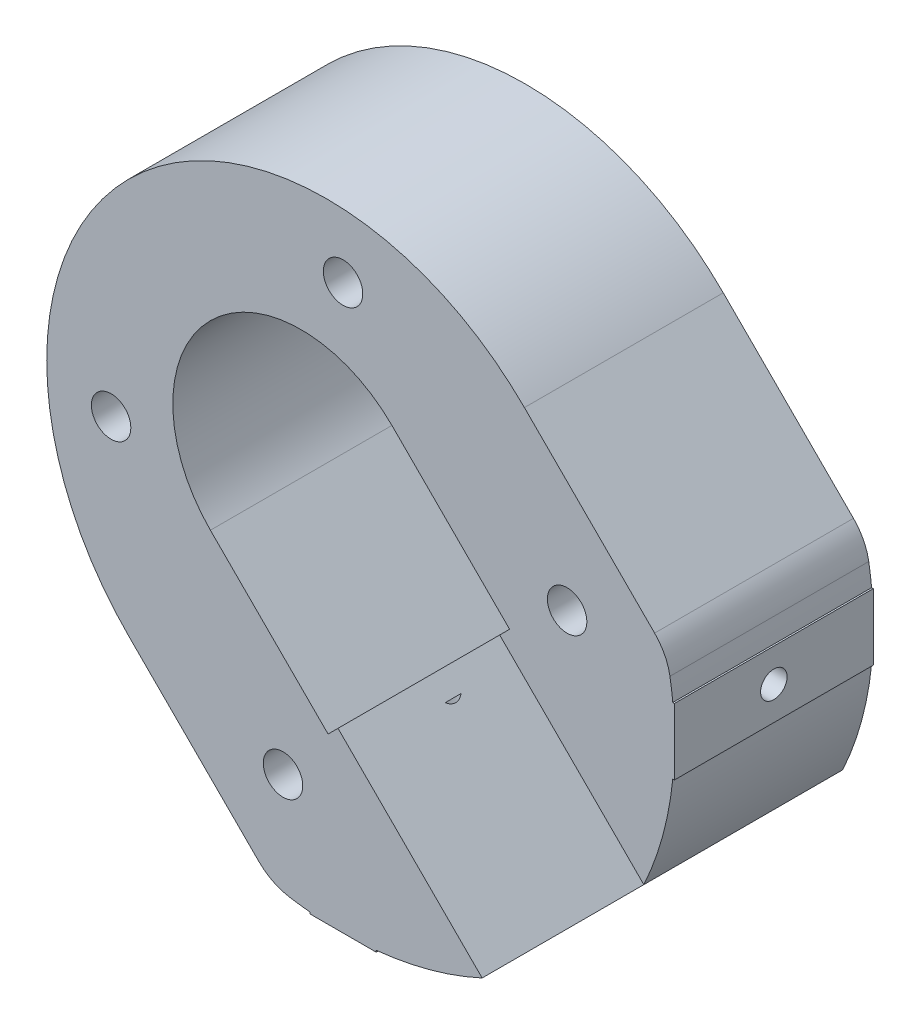
SolidWorks part; units mm, degrees
ref_plane "Front Plane" through (0, 0, 0) normal (0, 0, 1) x (1, 0, 0)
ref_plane "Top Plane" through (0, 0, 0) normal (0, 1, 0) x (1, 0, 0)
ref_plane "Right Plane" through (0, 0, 0) normal (1, 0, 0) x (0, 0, -1)
ref_axis "Z" through (0, 0, 33.5996) along (0, 0, -1)
ref_axis "X" through (56.0652, 0, 0) along (-1, 0, 0)
ref_axis "Y" through (0, -54.2845, 0) along (0, 1, 0)
sketch "Sketch1" plane through (0, 0, 0) normal (0, 0, 1) x (1, 0, 0)
  line L0 (5, -50) -> (-5, -50)
  line L1 (50, 5) -> (50, -5)
  line L2 (56.0652, 0) -> (-1.1166, 0) construction
  line L3 (0, -54.2845) -> (0, 1.1167) construction
  line L4 (61.712, 0) -> (50, 0) construction
  line L5 (0, -50) -> (0, -57.4075) construction
  line L6 (50, -5) -> (49.7494, -5)
  line L7 (5, -49.7494) -> (5, -50)
  line L10 (65.572, -65.572) -> (0, 0) construction
  line L20 (-5, -50) -> (-5, -49.7494)
  line L21 (49.7494, 5) -> (50, 5)
  line L22 (20.987, -45.3822) -> (-0.7634, -23.6318)
  line L23 (45.3822, -20.987) -> (23.6318, 0.7634)
  line L25 (-0.7634, -23.6318) -> (-2.2604, -25.1287)
  line L26 (-2.2604, -25.1287) -> (-20.0175, -7.3715)
  line L27 (23.6318, 0.7634) -> (25.1287, 2.2604)
  line L28 (25.1287, 2.2604) -> (7.3715, 20.0175)
  line L29 (-12.6985, -47.012) -> (-32.3444, -27.3661)
  line L30 (47.012, 12.6985) -> (27.3661, 32.3444)
  circle A0 centre (0, 0) radius 50 construction
  circle A1 centre (0, 0) radius 3.535 construction
  arc A2 (49.7494, -5) -> (5, -49.7494) centre (0, 0) cw construction
  arc A6 (49.7494, 5) -> (49.3214, 8.2098) centre (0, 0) ccw
  arc A7 (5, -49.7494) -> (20.987, -45.3822) centre (0, 0) ccw
  arc A8 (49.7494, -5) -> (45.3822, -20.987) centre (0, 0) cw
  arc A9 (7.3715, 20.0175) -> (-20.0175, -7.3715) centre (-6.323, 6.323) ccw
  arc A10 (-8.2098, -49.3214) -> (-12.6985, -47.012) centre (-6.8523, -41.1658) cw
  arc A12 (-8.2098, -49.3214) -> (-5, -49.7494) centre (0, 0) ccw
  arc A13 (35.3553, -35.3553) -> (-8.2098, -49.3214) centre (0, 0) ccw construction
  arc A15 (49.3214, 8.2098) -> (47.012, 12.6985) centre (41.1658, 6.8523) ccw
  arc A17 (49.3214, 8.2098) -> (35.3553, -35.3553) centre (0, 0) ccw construction
  arc A18 (27.3661, 32.3444) -> (-32.3444, -27.3661) centre (-2.4891, 2.4891) ccw
  dimension "D1" = 100
  dimension "D2" = 7.07
  dimension "D3" = 10
  dimension "D4" = 45
  dimension "D5" = 34.5
extrude "Boss-Extrude1" add sketch "Sketch1" against normal blind 15 and the other way blind 15
sketch "Sketch2" plane through (0, -50, 0) normal (0, 1, 0) x (1, 0, 0)
  line L0 (-57.5886, 0) -> (57.5886, 0) construction
  line L1 (0, -20.5521) -> (0, 20.5521) construction
  circle A0 centre (0, 0) radius 2
  dimension "D1" = 4
extrude "Cut-Extrude1" cut sketch "Sketch2" along normal blind 24
sketch "Sketch3" plane through (50, 0, 0) normal (1, 0, 0) x (0, 0, -1)
  circle A0 centre (0, 0) radius 2
  dimension "D1" = 4
extrude "Cut-Extrude2" cut sketch "Sketch3" against normal blind 24
sketch "Sketch5" plane through (0, 0, 0) normal (0, 0, 1) x (1, 0, 0)
  line L0 (0, 0) -> (0, -66.8046) construction
  dimension "D1" = 66.8046
ref_plane "Vert" through (0, 0, 0) normal (0.7071, 0.7071, 0) x (0, 0, -1)
sketch "Sketch6" plane through (0, 0, 0) normal (0, 0, 1) x (1, 0, 0)
  line L0 (0, 0) -> (-9.0587, -33.8074) construction
  line L1 (0, 0) -> (18.8244, -18.8244) construction
  line L2 (0, -54.2845) -> (0, 1.1167) construction
  line L3 (0, 0) -> (-35, 0) construction
  circle A0 centre (-9.0587, -33.8074) radius 2.9766
  circle A1 centre (-35, 0) radius 2.9766
  circle A2 centre (0, 35) radius 2.9766
  circle A3 centre (33.8074, 9.0587) radius 2.9766
  dimension "D4" = 5.9531
  dimension "D1" = 35
  dimension "D2" = 45
  dimension "D3" = 60
extrude "Cut-Extrude4" cut sketch "Sketch6" along normal through all
equation "\"EyeDiameter\" = 99.60916292"
equation "\"BasePlaneDistance\" = \"EyeDiameter\"/2+\"L2Thickness\"+\"EyeClearance\""
equation "\"EyeClearance\" = 2"
equation "\"EyeOD\"= \"EyeDiameter\""
equation "\"D2@Sketch1\"= 7.07"
equation "\"pinHoleDiameter\"=4"
equation "\"D1@Sketch2\"=\"pinHoleDiameter\""
equation "\"D1@Sketch3\"=\"pinHoleDiameter\""
equation "\"D1@Sketch5\"=\"BasePlaneDistance\""
equation "\"L2_ID\" = 20"
equation "\"vx\" = 0"
equation "\"vy\" = 0"
equation "\"vz\" = 200"
equation "\"parametric_end\" = 1"
equation "\"Rw_3_xx\" = -(\"vz\")/sqr((\"vx\")^2 + (\"vz\")^2)"
equation "\"Rw_3_xy\" = 0"
equation "\"Rw_3_xz\" = (\"vx\")/sqr((\"vx\")^2 + (\"vz\")^2)"
equation "\"Rw_3_zx\" = (\"vx\")/sqr((\"vx\")^2 + (\"vy\")^2 + (\"vz\")^2)"
equation "\"Rw_3_zy\" = (\"vy\")/sqr((\"vx\")^2 + (\"vy\")^2 + (\"vz\")^2)"
equation "\"Rw_3_zz\" = (\"vz\")/sqr((\"vx\")^2 + (\"vy\")^2 + (\"vz\")^2)"
equation "\"Rw_3_yx\" = (\"vx\")*(\"vy\")/sqr((\"vx\")^4 + (\"vx\")^2*(\"vy\")^2 + 2*(\"vx\")^2*(\"vz\")^2 + (\"vy\")^2*(\"vz\")^2 + (\"vz\")^4)"
equation "\"Rw_3_yy\" = -sqr((\"vx\")^2 + (\"vz\")^2)/sqr((\"vx\")^2 + (\"vy\")^2 + (\"vz\")^2)"
equation "\"Rw_3_yz\" = (\"vy\")*(\"vz\")/sqr((\"vx\")^4 + (\"vx\")^2*(\"vy\")^2 + 2*(\"vx\")^2*(\"vz\")^2 + (\"vy\")^2*(\"vz\")^2 + (\"vz\")^4)"
equation "\"O2Targx\" = -\"BasePlaneDistance\"*(\"vx\")*(\"vy\")/sqr((\"vx\")^4 + (\"vx\")^2*(\"vy\")^2 + 2*(\"vx\")^2*(\"vz\")^2 + (\"vy\")^2*(\"vz\")^2 + (\"vz\")^4)"
equation "\"O2Targy\" = \"BasePlaneDistance\"*sqr((\"vx\")^2 + (\"vz\")^2)/sqr((\"vx\")^2 + (\"vy\")^2 + (\"vz\")^2)"
equation "\"O2Targz\" = -\"BasePlaneDistance\"*(\"vy\")*(\"vz\")/sqr((\"vx\")^4 + (\"vx\")^2*(\"vy\")^2 + 2*(\"vx\")^2*(\"vz\")^2 + (\"vy\")^2*(\"vz\")^2 + (\"vz\")^4)"
equation "\"O2Targx_0\" = -(\"BasePlaneDistance\")*sqr((\"vx\")^2 + (\"vz\")^2)/sqr((\"vx\")^2 + (\"vy\")^2 + (\"vz\")^2)"
equation "\"O2Targy_0\" = -(\"BasePlaneDistance\")*(\"vy\")*(\"vz\")/sqr((\"vx\")^4 + (\"vx\")^2*(\"vy\")^2 + 2*(\"vx\")^2*(\"vz\")^2 + (\"vy\")^2*(\"vz\")^2 + (\"vz\")^4)"
equation "\"O2Targz_0\" = (\"BasePlaneDistance\")*(\"vx\")*(\"vy\")/sqr((\"vx\")^4 + (\"vx\")^2*(\"vy\")^2 + 2*(\"vx\")^2*(\"vz\")^2 + (\"vy\")^2*(\"vz\")^2 + (\"vz\")^4) + (\"BasePlaneDistance\")"
equation "\"theta2_s1\" = arcsin(((\"BasePlaneDistance\") - (\"O2Targz_0\"))/(\"BasePlaneDistance\")) + pi"
equation "\"theta2_s2\" = -arcsin(((\"BasePlaneDistance\") - (\"O2Targz_0\"))/(\"BasePlaneDistance\"))"
equation "\"theta1_s1\" = arcsin((\"O2Targy_0\")/((\"BasePlaneDistance\")*cos((\"Theta2\")))) + pi"
equation "\"theta1_s2\" = -arcsin((\"O2Targy_0\")/((\"BasePlaneDistance\")*cos((\"Theta2\"))))"
equation "\"theta1_s3\" = -arccos(-(\"O2Targx_0\")/((\"BasePlaneDistance\")*cos((\"Theta2\")))) + 2*pi"
equation "\"theta1_s4\" = arccos(-(\"O2Targx_0\")/((\"BasePlaneDistance\")*cos((\"Theta2\"))))"
equation "\"Theta1\" = \"theta1_s2\" 'so far, theta1_s1 and theta1_s4 have agreed, and they agree with the sw constraint solver"
equation "\"Theta2\" = \"theta2_s2\""
equation "\"o2_x\" = -(\"BasePlaneDistance\")*cos((\"Theta1\"))*cos((\"Theta2\"))"
equation "\"o2_y\" = -(\"BasePlaneDistance\")*sin((\"Theta1\"))*cos((\"Theta2\"))"
equation "\"o2_z\" = (\"BasePlaneDistance\")*(sin((\"Theta2\")) + 1)"
equation "\"o1_x\" = (\"BasePlaneDistance\")*sin((\"Theta1\"))"
equation "\"o1_y\" = -(\"BasePlaneDistance\")*cos((\"Theta1\"))"
equation "\"o1_z\" = (\"BasePlaneDistance\")"
equation "\"Actuator1_Theta\" = atn(\"vx\"/\"vz\") 'ik solution for the single link joint"
equation "\"Actuator2_Theta\" = \"Theta1\"  'ik solution for the double link joint"
equation "\"MotorBaseThickness\" = 3 "
equation "\"BaseThickness\" = 3 "
equation "\"EncoderToMagnetAirgap\" = 1 'Encoder to magnet airgap"
equation "\"EncoderHeight\" = 1.192  'Height of the encoder"
equation "\"MagnetThickness\" = 0.5  'Magnet thickness"
equation "\"pcb_thickness\" = 1.6  'Thickness of the PCB"
equation "\"pcb_outer_diameter\" = 32 'the OD of the pcb"
equation "\"shaft_diameter\" = 4"
equation "\"L2Thickness\" = 3.75 * \"shaft_diameter\""
equation "\"D1@Cut-Extrude2\"=\"shaft_diameter\"*6"
equation "\"D1@Cut-Extrude1\"=\"shaft_diameter\"*6"
